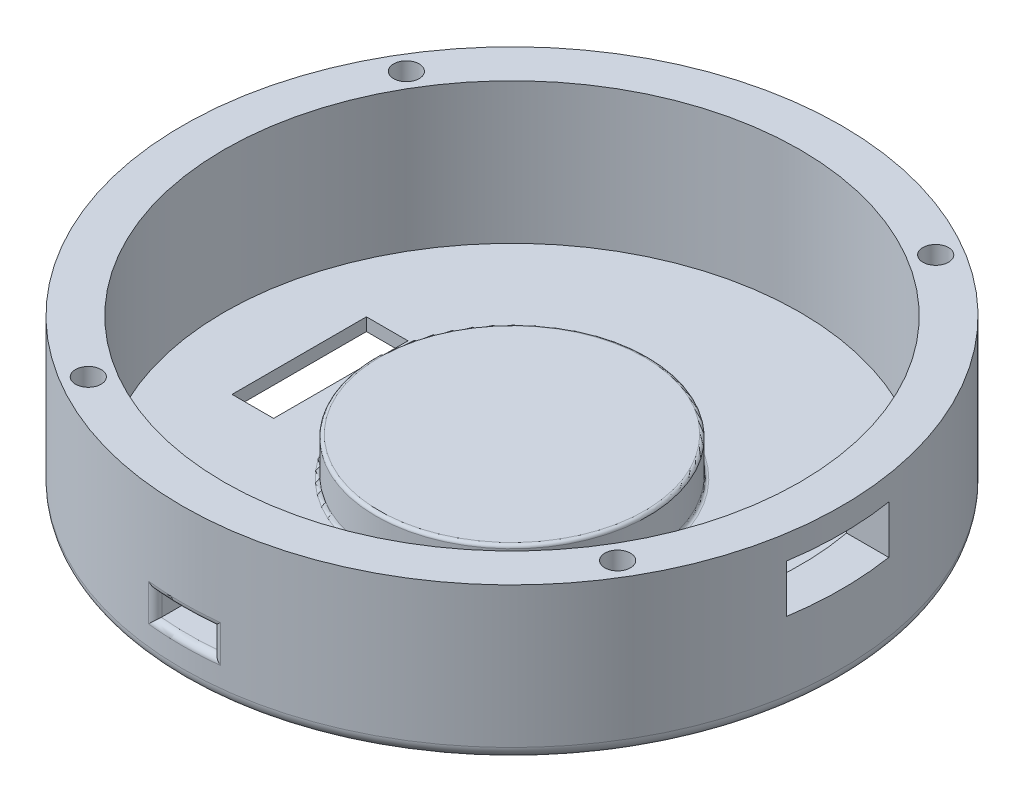
SolidWorks part; units mm, degrees
ref_plane "Front Plane" through (0, 0, 0) normal (0, 0, 1) x (1, 0, 0)
ref_plane "Top Plane" through (0, 0, 0) normal (0, 1, 0) x (1, 0, 0)
ref_plane "Right Plane" through (0, 0, 0) normal (1, 0, 0) x (0, 0, -1)
sketch "Sketch1" plane through (0, 0, 0) normal (0, 1, 0) x (1, 0, 0)
  circle A0 centre (0, 0) radius 51.5
  dimension "D1" = 103
extrude "Boss-Extrude1" add sketch "Sketch1" along normal blind 24 contours A0
sketch "Sketch2" plane through (0, 24, 0) normal (0, 1, 0) x (1, 0, 0)
  circle A0 centre (0, 0) radius 45
  dimension "D1" = 90
extrude "Cut-Extrude1" cut sketch "Sketch2" against normal blind 22
fillet "Fillet1" radius 2 1 edges at (0, 0, 51.5)
ref_plane "Plane2" through (0, 0, 40) normal (0, 0, 1) x (1, 0, 0)
sketch "Sketch9" plane through (0, 0, 40) normal (0, 0, 1) x (1, 0, 0)
  line L0 (51.5, 2) -> (-51.5, 2) construction
  line L1 (4.5, 6.1) -> (-4.5, 6.1)
  line L3 (4.5, 9.9) -> (-4.5, 9.9)
  line L5 (4.5, 6.1) -> (-4.5, 9.9) construction
  line L6 (4.5, 9.9) -> (-4.5, 6.1) construction
  line L7 (-4.5, 9.9) -> (-4.5, 6.1) construction
  line L8 (4.5, 9.9) -> (4.5, 6.1) construction
  line L9 (4.5, 9.9) -> (4.5, 6.1)
  line L10 (-4.5, 9.9) -> (-4.5, 6.1)
  point P0 (0, 8)
  dimension "D1" = 9
  dimension "D2" = 3.8
  dimension "D3" = 6
extrude "Cut-Extrude13" cut sketch "Sketch9" along normal blind 20 contours L3 L10 L1 L9
fillet "Fillet2" radius 1 4 edges at (4.5, 8, 51.303) (0, 9.9, 51.5) (-4.5, 8, 51.303) (0, 6.1, 51.5)
sketch "Sketch10" plane through (0, 0, 0) normal (0, -1, 0) x (1, 0, 0)
  line L1 (-26.75, -10.5) -> (-33.25, -10.5)
  line L2 (-26.75, -10.5) -> (-26.75, 10.5)
  line L3 (-26.75, 10.5) -> (-33.25, 10.5)
  line L4 (-33.25, -10.5) -> (-33.25, 10.5)
  line L5 (-26.75, -10.5) -> (-33.25, 10.5) construction
  line L6 (-26.75, 10.5) -> (-33.25, -10.5) construction
  point P0 (-30, 0)
  dimension "D1" = 21
  dimension "D2" = 6.5
  dimension "D3" = 30
extrude "Cut-Extrude14" cut sketch "Sketch10" against normal blind 8
sketch "Sketch11" plane through (0, 0, 0) normal (0, -1, 0) x (1, 0, 0)
  circle A0 centre (0, 0) radius 21.25
  dimension "D1" = 42.5
sketch "Sketch13" plane through (0, 24, 0) normal (0, 1, 0) x (1, 0, 0)
  line L0 (0, 0) -> (-41.3583, 24.8506) construction
  line L1 (0, 0) -> (-24.8506, -41.3583) construction
  line L2 (0, 0) -> (41.3583, -24.8506) construction
  line L3 (0, 0) -> (24.8506, 41.3583) construction
  line L4 (0, 0) -> (0, 49.86) construction
  circle A0 centre (24.8506, 41.3583) radius 2
  circle A1 centre (41.3583, -24.8506) radius 2
  circle A2 centre (-24.8506, -41.3583) radius 2
  circle A3 centre (-41.3583, 24.8506) radius 2
  dimension "D2" = 4
  dimension "D1" = 48.25
  dimension "D3" = 59
extrude "Cut-Extrude16" cut sketch "Sketch13" against normal through all
extrude "Boss-Extrude2" add sketch "Sketch11" against normal blind 8
ref_plane "Plane3" through (51.5, 0, 0) normal (1, 0, 0) x (0, 0, -1)
sketch "Sketch15" plane through (51.5, 0, 0) normal (1, 0, 0) x (0, 0, -1)
  line L0 (0, 0) -> (0, 24) construction
  line L1 (51.5, 24) -> (-51.5, 24) construction
  circle A0 centre (0, 16.5) radius 2
  dimension "D1" = 4
  dimension "D2" = 7.5
extrude "Cut-Extrude18" cut sketch "Sketch15" against normal blind 2
ref_plane "Plane4" through (45, 0, 0) normal (1, 0, 0) x (0, 0, -1)
ref_plane "Plane5" through (49.5, 0, 0) normal (1, 0, 0) x (0, 0, -1)
sketch "Sketch17" plane through (45, 0, 0) normal (1, 0, 0) x (0, 0, -1)
  line L1 (-8, 12.75) -> (8, 12.75)
  line L2 (-8, 12.75) -> (-8, 20.25)
  line L3 (-8, 20.25) -> (8, 20.25)
  line L4 (8, 12.75) -> (8, 20.25)
  line L5 (-8, 12.75) -> (8, 20.25) construction
  line L6 (-8, 20.25) -> (8, 12.75) construction
  point P0 (0, 16.5)
  dimension "D1" = 16
  dimension "D2" = 7.5
wrap "Wrap4" sketch "Sketch17" wrap type scribe source sketch "Sketch17" face at (0, 8, 44.8872)
extrude "Cut-Extrude37" cut sketch "Sketch17<2>" along normal blind 12 and the other way blind 5.7 from offset 0.5
sketch "Sketch17<2>" plane through (45, 0, 0) normal (1, 0, 0) x (0, 0, -1) same geometry as "Sketch17"
sketch "Sketch18" plane through (0, 0, 0) normal (0, -1, 0) x (1, 0, 0)
  circle A0 centre (0, 0) radius 20
  dimension "D1" = 40
extrude "Cut-Extrude39" cut sketch "Sketch18" against normal blind 6
fillet "Fillet3" radius 0.5 1 edges at (0, 8, -21.25)
fillet "Fillet4" radius 0.5 1 edges at (0, 2, 21.25)
